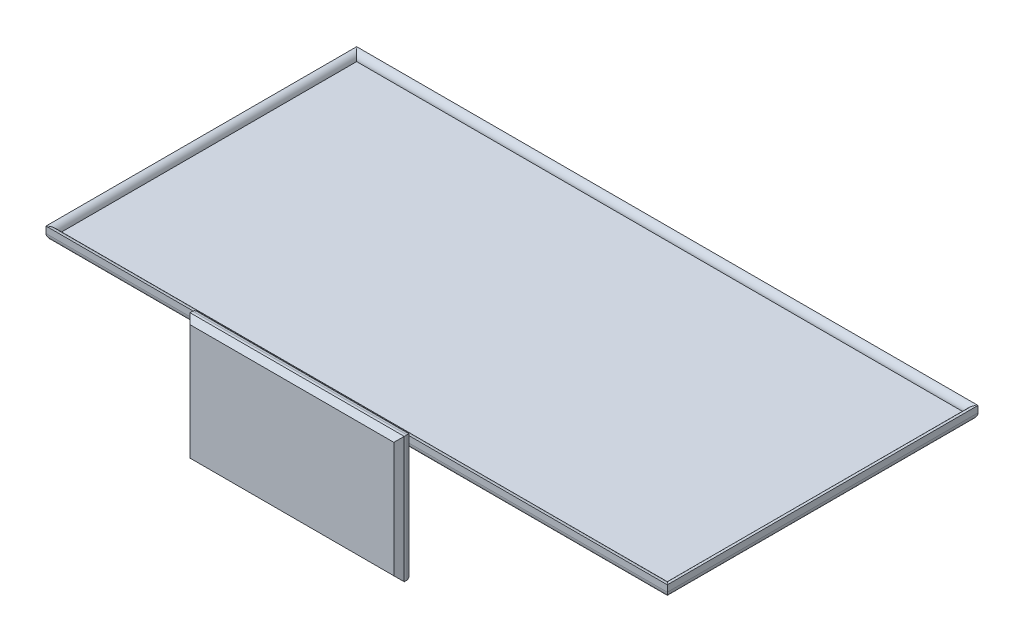
SolidWorks part; units mm, degrees
ref_plane "Front Plane" through (0, 0, 0) normal (0, 0, 1) x (1, 0, 0)
ref_plane "Top Plane" through (0, 0, 0) normal (0, 1, 0) x (1, 0, 0)
ref_plane "Right Plane" through (0, 0, 0) normal (1, 0, 0) x (0, 0, -1)
sketch "Sketch1" plane through (0, 0, 0) normal (0, 1, 0) x (1, 0, 0)
  line L1 (-6, -3) -> (6, -3)
  line L2 (-6, -3) -> (-6, 3)
  line L3 (-6, 3) -> (6, 3)
  line L4 (6, -3) -> (6, 3)
  line L5 (-6, -3) -> (6, 3) construction
  line L6 (-6, 3) -> (6, -3) construction
  point P0 (0, 0)
  dimension "D1" = 6
  dimension "D2" = 12
extrude "Boss-Extrude1" add sketch "Sketch1" along normal blind 0.25
sketch3d "3DSketch1"
  line L0 (-5.875, 0.25, -2.875) -> (-5.875, 0.25, 2.875)
  line L1 (-5.875, 0.25, 2.875) -> (5.875, 0.25, 2.875)
  line L2 (5.875, 0.25, 2.875) -> (5.875, 0.25, -2.875)
  line L3 (5.875, 0.25, -2.875) -> (-5.875, 0.25, -2.875)
  line L4 (-5.875, 0.25, -2.875) -> (-5.875, 0.25, 2.875)
  line L5 (-5.875, 0.25, 2.875) -> (5.875, 0.25, 2.875)
  line L6 (5.875, 0.25, 2.875) -> (5.875, 0.25, -2.875)
  line L7 (5.875, 0.25, -2.875) -> (-5.875, 0.25, -2.875)
  dimension "D1" = 0.125
extrude "Cut-Extrude1" cut sketch "3DSketch1" along direction (0, -1, 0) on the side of the normal blind 0.125
sketch "Sketch2" plane through (0, 0, 3) normal (0, 0, 1) x (1, 0, 0)
  line L0 (-6, 0.25) -> (6, 0.25) construction
  line L1 (-0.1514, 0) -> (0.1486, 0)
  line L2 (-0.1514, 0) -> (-0.1514, 0.25)
  line L3 (-0.1514, 0.25) -> (0.1486, 0.25)
  line L4 (0.1486, 0) -> (0.1486, 0.25)
  line L5 (-0.1514, 0) -> (0.1486, 0.25) construction
  line L6 (-0.1514, 0.25) -> (0.1486, 0) construction
  point P0 (-0.0014, 0.125)
  dimension "D1" = 0.25
  dimension "D2" = 0.3
extrude "Boss-Extrude2" add sketch "Sketch2" along normal blind 1
ref_plane "Plane1" through (0, 0, 4) normal (0, 0, 1) x (1, 0, 0)
sketch "Sketch4" plane through (0, 0, 4) normal (0, 0, 1) x (1, 0, 0)
  line L1 (-2.0681, -1.0913) -> (2.0681, -1.0913)
  line L2 (-2.0681, -1.0913) -> (-2.0681, 1.3413)
  line L3 (-2.0681, 1.3413) -> (2.0681, 1.3413)
  line L4 (2.0681, -1.0913) -> (2.0681, 1.3413)
  line L5 (-2.0681, -1.0913) -> (2.0681, 1.3413) construction
  line L6 (-2.0681, 1.3413) -> (2.0681, -1.0913) construction
  point P0 (0, 0.125)
extrude "Boss-Extrude3" add sketch "Sketch4" along normal blind 0.25
fillet "Fillet2" radius 0.1 4 edges at (-2.0681, 0.125, 4) (0, -1.0913, 4) (2.0681, 0.125, 4) (0, 1.3413, 4)
chamfer "Chamfer1" distance 0.1 angle 45 4 edges at (-2.0681, 0.125, 4.25) (0, -1.0913, 4.25) (2.0681, 0.125, 4.25) (0, 1.3413, 4.25)
fillet "Fillet3" radius 0.125 4 edges
chamfer "Chamfer2" distance 0.1 angle 45 4 edges at (0.1486, 0, 3.5) (-0.1514, 0, 3.5) (0.1486, 0.25, 3.5) (-0.1514, 0.25, 3.5)
fillet "Fillet4" radius 0.125 5 edges at (6, 0, 0) (3.0243, 0, 3) (-3.0257, 0, 3) (-6, 0, 0) (0, 0, -3)
